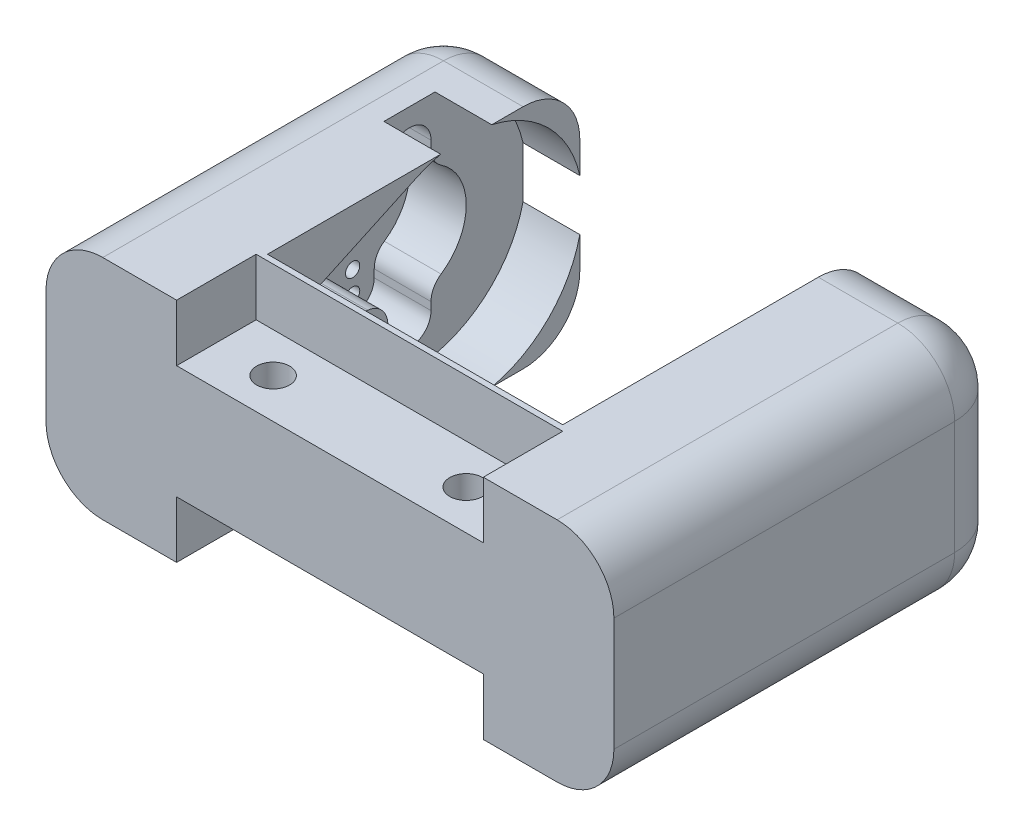
SolidWorks part; units mm, degrees
ref_plane "Спереди" through (0, 0, 0) normal (0, 0, 1) x (1, 0, 0)
ref_plane "Сверху" through (0, 0, 0) normal (0, 1, 0) x (1, 0, 0)
ref_plane "Справа" through (0, 0, 0) normal (1, 0, 0) x (0, 0, -1)
sketch "Эскиз1" plane through (0, 0, 0) normal (0, 1, 0) x (1, 0, 0)
  line L0 (-13, 27.5) -> (-13, 0)
  line L1 (-25, -7.5) -> (25, -7.5)
  line L2 (-25, -7.5) -> (-25, 27.5)
  line L3 (-25, 27.5) -> (-13, 27.5)
  line L4 (25, -7.5) -> (25, 27.5)
  line L5 (-25, -7.5) -> (25, 27.5) construction
  line L6 (-25, 27.5) -> (25, -7.5) construction
  line L7 (-13, 0) -> (13, 0)
  line L8 (13, 0) -> (13, 27.5)
  line L9 (13, 27.5) -> (25, 27.5)
  dimension "D1" = 27.5
  dimension "D2" = 50
  dimension "D3" = 26
  dimension "D4" = 35
extrude "Бобышка-Вытянуть1" add sketch "Эскиз1" along normal blind 20
fillet "Скругление1" radius 5 10 edges at (25, 0, -10) (25, 20, -10) (-25, 20, -10) (-25, 0, -10) (19, 20, -27.5) (25, 10, -27.5) (19, 0, -27.5) (-25, 10, -27.5) (-19, 20, -27.5) (-19, 0, -27.5)
sketch "Эскиз2" plane through (13, 0, 0) normal (-1, 0, 0) x (0, 0, 1)
  line L0 (-1030, 10) -> (48970, 10) construction
  line L1 (-27.5, 5) -> (-27.5, 15) construction
  circle A0 centre (-17.5, 10) radius 8
  point P5 (-27.5, 10)
  dimension "D1" = 16
  dimension "D2" = 10
extrude "Вырез-Вытянуть1" cut sketch "Эскиз2" against normal blind 5
sketch "Эскиз3" plane through (18, 0, 0) normal (-1, 0, 0) x (0, 0, 1)
  circle A0 centre (-17.5, 10) radius 6
  circle A1 centre (-17.5, 10) radius 8 construction
  dimension "D1" = 12
extrude "Вырез-Вытянуть2" cut sketch "Эскиз3" against normal blind 1
sketch "Эскиз4" plane through (-13, 0, 0) normal (1, 0, 0) x (0, 0, -1)
  line L0 (-1015, 10) -> (48985, 10) construction
  line L1 (-7.5, 15) -> (-7.5, 5) construction
  line L2 (13.195, 19.3021) -> (2.9, 14.5376)
  line L3 (2.9, 5.4624) -> (13.195, 0.6979)
  arc A0 (13.195, 0.6979) -> (13.195, 19.3021) centre (17.5, 10) ccw
  circle A1 centre (17.5, 10) radius 8 construction
  arc A2 (2.9, 14.5376) -> (2.9, 5.4624) centre (5, 10) ccw
  point P7 (-7.5, 10)
  dimension "D1" = 20.5
  dimension "D2" = 12.5
  dimension "D3" = 5
extrude "Вырез-Вытянуть3" cut sketch "Эскиз4" against normal blind 5
sketch "Эскиз5" plane through (-18, 0, 0) normal (1, 0, 0) x (0, 0, -1)
  line L0 (19.4, 15.8129) -> (19.4, 16.4984)
  line L1 (15.6, 16.4984) -> (15.6, 15.6654)
  line L2 (13.8328, 13.679) -> (1.9323, 12.2844)
  line L3 (1.9323, 7.7156) -> (13.8328, 6.321)
  line L4 (15.6, 4.3346) -> (15.6, 3.5016)
  line L5 (19.4, 3.5016) -> (19.4, 4.1871)
  arc A0 (19.4, 16.4984) -> (15.6, 16.4984) centre (17.5, 16.4984) ccw
  arc A1 (1.9323, 12.2844) -> (1.9323, 7.7156) centre (2.2, 10) ccw
  arc A2 (15.6, 3.5016) -> (19.4, 3.5016) centre (17.5, 3.5016) ccw
  arc A4 (20.2857, 14.1521) -> (20.2857, 5.8479) centre (17.5, 10) cw
  arc A5 (15.6, 4.3346) -> (13.8328, 6.321) centre (13.6, 4.3346) ccw
  arc A6 (15.6, 15.6654) -> (13.8328, 13.679) centre (13.6, 15.6654) cw
  arc A7 (20.2857, 5.8479) -> (19.4, 4.1871) centre (21.4, 4.1871) ccw
  arc A8 (20.2857, 14.1521) -> (19.4, 15.8129) centre (21.4, 15.8129) cw
  arc A9 (15.25, 20) -> (13.195, 19.3021) centre (17.5, 10) ccw construction
  arc A10 (15.25, 20) -> (13.195, 19.3021) centre (17.5, 10) ccw construction
  dimension "D3" = 2.3
  dimension "D4" = 1.9
  dimension "D5" = 5
  dimension "D8" = 2
  dimension "D9" = 2
  dimension "D1" = 3.8
  dimension "D2" = 15.3
  dimension "D6" = 12.9968
  dimension "D7" = 0.833
extrude "Вырез-Вытянуть4" cut sketch "Эскиз5" against normal blind 5
sketch "Эскиз6" plane through (-23, 0, 0) normal (1, 0, 0) x (0, 0, -1)
  line L0 (-990.222, 10) -> (49009.778, 10) construction
  line L1 (22.5, 5) -> (22.5, 15) construction
  line L2 (17.5, -985.0921) -> (17.5, 49014.9079) construction
  circle A0 centre (2.278, 10) radius 0.625
  circle A1 centre (6.3111, 10) radius 0.625
  circle A2 centre (10.4282, 10) radius 0.625
  circle A3 centre (17.5, 14.9079) radius 0.625
  circle A4 centre (17.5, 16.8489) radius 0.625
  circle A5 centre (17.5, 5.0821) radius 0.625
  circle A6 centre (17.5, 3.1411) radius 0.625
  point P11 (24009.778, 10)
  point P14 (22.5, 10)
  dimension "D1" = 1.25
  dimension "D2" = 4.0331
  dimension "D3" = 4.1171
  dimension "D4" = 12.0718
  dimension "D5" = 4.9079
  dimension "D6" = 1.9409
  dimension "D7" = 4.9179
  dimension "D8" = 1.9409
  dimension "D9" = 5
extrude "Вырез-Вытянуть5" cut sketch "Эскиз6" against normal blind 4
sketch "Эскиз7" plane through (0, 0, 7.5) normal (0, 0, 1) x (1, 0, 0)
  line L0 (-20, 20) -> (20, 20) construction
  line L1 (-13.5, 20) -> (13.5, 20)
  line L2 (-13.5, 20) -> (-13.5, 15)
  line L3 (-13.5, 15) -> (13.5, 15)
  line L4 (13.5, 20) -> (13.5, 15)
  line L5 (-25, 15) -> (-25, 5) construction
  line L6 (25, 15) -> (25, 5) construction
  line L7 (-20, 0) -> (20, 0) construction
  line L8 (-13.5, 0) -> (13.5, 0)
  line L9 (-13.5, 0) -> (-13.5, 5)
  line L10 (-13.5, 5) -> (13.5, 5)
  line L11 (13.5, 0) -> (13.5, 5)
  dimension "D1" = 11.5
  dimension "D2" = 11.5
  dimension "D3" = 5
extrude "Вырез-Вытянуть6" cut sketch "Эскиз7" against normal blind 7
sketch "Эскиз8" plane through (0, 15, 0) normal (0, 1, 0) x (1, 0, 0)
  line L0 (-1013.5, -4) -> (48986.5, -4) construction
  line L1 (-13.5, -0.5) -> (-13.5, -7.5) construction
  line L2 (-13.5, -0.5) -> (-13.5, -7.5) construction
  line L3 (13.5, -0.5) -> (13.5, -7.5) construction
  circle A0 centre (-8.5, -4) radius 1.45
  circle A1 centre (8.5, -4) radius 1.45
  point P5 (-8.5069, -9)
  point P9 (-13.5, -4)
  point P10 (9.0939, -9)
  dimension "D1" = 5
  dimension "D2" = 2.9
  dimension "D3" = 5
extrude "Вырез-Вытянуть7" cut sketch "Эскиз8" against normal blind 12
